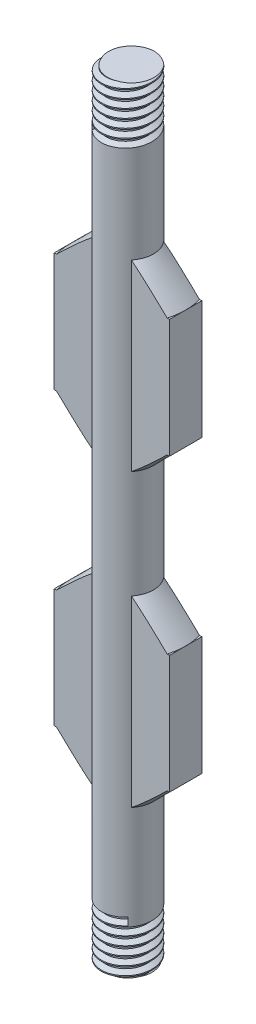
SolidWorks part; units mm, degrees
ref_plane "Front Plane" through (0, 0, 0) normal (0, 0, 1) x (1, 0, 0)
ref_plane "Top Plane" through (0, 0, 0) normal (0, 1, 0) x (1, 0, 0)
ref_plane "Right Plane" through (0, 0, 0) normal (1, 0, 0) x (0, 0, -1)
sketch "Sketch1" plane through (0, 0, 0) normal (0, 1, 0) x (1, 0, 0)
  circle A0 centre (0, 0) radius 2.35
  dimension "D1" = 4.7
extrude "Boss-Extrude1" add sketch "Sketch1" along normal blind 14
extrude "Boss-Extrude2" add sketch "Sketch1<2>" along normal blind 3 from surface starting at face at (0, 14, 2.35)
sketch "Sketch1<2>" plane through (0, 0, 0) normal (0, 1, 0) x (1, 0, 0) same geometry as "Sketch1"
sketch "Sketch2" plane through (0, 17, 0) normal (0, 1, 0) x (1, 0, 0)
  line L0 (-1.809, -1.5) -> (-5.35, -1.5)
  line L1 (-5.35, -1.5) -> (-5.35, 1.5)
  line L2 (-5.35, 1.5) -> (-1.809, 1.5)
  line L3 (0, 2.35) -> (0, -2.35) construction
  line L4 (-2.35, 0) -> (-5.35, 0) construction
  line L5 (0, 0) -> (-2.35, 0) construction
  line L6 (5.35, 1.5) -> (1.809, 1.5)
  line L7 (5.35, -1.5) -> (5.35, 1.5)
  line L8 (1.809, -1.5) -> (5.35, -1.5)
  arc A0 (-1.809, 1.5) -> (-2.35, 0) centre (0, 0) ccw construction
  circle A1 centre (0, 0) radius 2.35
  arc A2 (-1.809, -1.5) -> (1.809, -1.5) centre (0, 0) ccw
  arc A3 (-2.35, 0) -> (-1.809, -1.5) centre (0, 0) ccw construction
  arc A4 (1.809, 1.5) -> (-1.809, 1.5) centre (0, 0) ccw
  arc A5 (1.809, -1.5) -> (1.809, 1.5) centre (0, 0) ccw construction
  point P10 (0, 0)
  point P12 (-5.35, 0)
  dimension "D2" = 3
  dimension "D3" = 3
  dimension "D1" = 0
extrude "Boss-Extrude3" add sketch "Sketch2" along normal blind 11
extrude "Boss-Extrude4" add sketch "Sketch1<3>" along normal blind 16 from surface starting at face at (0, 28, 0)
sketch "Sketch1<3>" plane through (0, 0, 0) normal (0, 1, 0) x (1, 0, 0) same geometry as "Sketch1"
extrude "Boss-Extrude5" add sketch "Sketch2<2>" along normal blind 11 from surface starting at face at (0, 44, 2.35)
sketch "Sketch2<2>" plane through (0, 17, 0) normal (0, 1, 0) x (1, 0, 0) same geometry as "Sketch2"
extrude "Boss-Extrude6" add sketch "Sketch1<4>" along normal blind 3 from surface starting at face at (0, 55, 0)
sketch "Sketch1<4>" plane through (0, 0, 0) normal (0, 1, 0) x (1, 0, 0) same geometry as "Sketch1"
extrude "Boss-Extrude7" add sketch "Sketch1<5>" along normal blind 14 from surface starting at face at (0, 58, 2.35)
sketch "Sketch1<5>" plane through (0, 0, 0) normal (0, 1, 0) x (1, 0, 0) same geometry as "Sketch1"
chamfer "Chamfer1" distance 3 angle 45 8 edges at (2.35, 55, 0) (-2.35, 55, 0) (-2.35, 44, 0) (2.35, 44, 0) (2.35, 28, 0) (-2.35, 28, 0) (-2.35, 17, 0) (2.35, 17, 0)
thread "Thread1" pitch 0.8 method cut profile "Thread Profile1" start angle 0, offset 1, length 5.5, pitch 0.8, diameter 4.7
ref_plane "Plane1" through (-2.35, 73, 0) normal (0, 0, 1) x (-1, 0, 0)
sketch "Thread Profile1" plane through (-2.35, 73, 0) normal (0, 0, 1) x (-1, 0, 0)
  line L0 (0, 0) -> (0, 0.8) construction
  line L11 (0, 0) -> (0, 0.7)
  line L12 (0, 0.7) -> (-0.433, 0.45)
  line L13 (-0.433, 0.45) -> (-0.433, 0.25)
  line L15 (-0.433, 0.25) -> (0, 0)
  line L17 (-0.433, 0.35) -> (0, 0.35) construction
  point P2 (0, 0)
  dimension "Pitch" = 0.8
  dimension "Profile_Angle" = 60
  dimension "Profile_Land" = 0.2
  dimension "Profile_Height" = 0.433
thread "Thread2" pitch 0.8 method cut profile "Thread Profile2" start angle 0, offset 1, length 5.5, pitch 0.8, diameter 4.7
ref_plane "Plane2" through (2.35, -1, 0) normal (0, 0, 1) x (1, 0, 0)
sketch "Thread Profile2" plane through (2.35, -1, 0) normal (0, 0, 1) x (1, 0, 0)
  line L0 (0, 0) -> (0, 0.8) construction
  line L11 (0, 0) -> (0, 0.7)
  line L12 (0, 0.7) -> (-0.433, 0.45)
  line L13 (-0.433, 0.45) -> (-0.433, 0.25)
  line L15 (-0.433, 0.25) -> (0, 0)
  line L17 (-0.433, 0.35) -> (0, 0.35) construction
  point P2 (0, 0)
  dimension "Pitch" = 0.8
  dimension "Profile_Angle" = 60
  dimension "Profile_Land" = 0.2
  dimension "Profile_Height" = 0.433
equation "\"OutExtension\"= 14"
equation "\"D1@Boss-Extrude1\"=\"OutExtension\""
equation "\"D1@Boss-Extrude7\"=\"OutExtension\""
